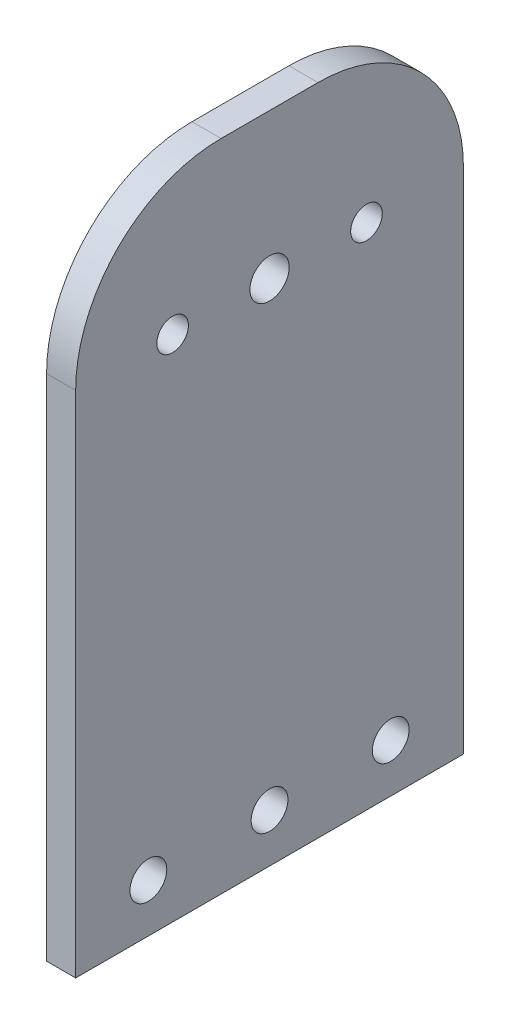
SolidWorks part; units mm, degrees
ref_plane "Front Plane" through (0, 0, 0) normal (0, 0, 1) x (1, 0, 0)
ref_plane "Top Plane" through (0, 0, 0) normal (0, 1, 0) x (1, 0, 0)
ref_plane "Right Plane" through (0, 0, 0) normal (1, 0, 0) x (0, 0, -1)
sketch "Sketch1" plane through (0, 0, 0) normal (1, 0, 0) x (0, 0, -1)
  line L1 (0, 0) -> (40, 0)
  line L2 (0, 0) -> (0, 52.5)
  line L3 (15, 67.5) -> (25, 67.5)
  line L4 (40, 0) -> (40, 52.5)
  arc A1 (25, 67.5) -> (40, 52.5) centre (25, 52.5) cw
  arc A2 (0, 52.5) -> (15, 67.5) centre (15, 52.5) cw
  point P7 (40, 67.5)
  point P10 (0, 67.5)
  dimension "D3" = 15
  dimension "D1" = 40
  dimension "D2" = 52.5
extrude "Boss-Extrude1" add sketch "Sketch1" along normal blind 3 contours L2 L1 L4 region at (0, 32.6224, -20)
ref_axis "Axis1" through (3, 67.5, -20) along (0, -1, 0)
ref_plane "Plane1" through (0, 0, -20) normal (0, 0, -1) x (-1, 0, 0)
hole_wizard "#6 Clearance Hole2" positions "Sketch6" profile "Sketch7" hole size "#6" standard "ANSI Inch" end condition through all
sketch "Sketch6" plane through (3, 0, 0) normal (1, 0, 0) x (0, 0, -1)
  line L0 (0, 0) -> (40, 0) construction
  line L1 (20, -49.3392) -> (20, 49.3392) construction
  point P0 (7.5, 5)
  point P2 (20, 5)
  point P8 (20, 0)
  point P11 (32.5, 5)
  dimension "D1" = 12.5
  dimension "D2" = 5
sketch "Sketch7" plane through (3, 5, -7.5) normal (0, 1, 0) x (0, 0, -1)
  line L0 (0, 0) -> (0, 3)
  line L1 (0, 3) -> (1.8986, 3)
  line L2 (1.8986, 3) -> (1.8986, 0)
  line L5 (1.8986, 0) -> (0, 0)
  line L11 (0, -6.35) -> (0, 107.95) construction
  dimension "Thru Hole Dia." = 3.7973
  dimension "Thru Hole Depth" = 3
sketch "Sketch10" plane through (3, 0, 0) normal (1, 0, 0) x (0, 0, -1)
  line L0 (0, 0) -> (40, 0) construction
  line L1 (20, 67.5) -> (20, -0.1097) construction
  circle A0 centre (20, 52.5) radius 2.025
  point P4 (0, 0)
  dimension "D2" = 4.05
  dimension "D1" = 52.5
extrude "Cut-Extrude1" cut sketch "Sketch10" against normal blind 10
hole_wizard "#4 Clearance Hole3" positions "Sketch11" profile "Sketch12" hole size "#4" standard "ANSI Inch" end condition through all
sketch "Sketch11" plane through (3, 0, 0) normal (1, 0, 0) x (0, 0, -1)
  line L0 (20, -49.3392) -> (20, 49.3392) construction
  circle A1 centre (20, 52.5) radius 2.025 construction
  point P0 (10, 52.5)
  point P5 (0, 0)
  point P8 (0, 0)
  point P12 (0, 0)
  point P13 (0, 0)
  point P16 (30, 52.5)
  dimension "D1" = 10
sketch "Sketch12" plane through (3, 52.5, -10) normal (0, 1, 0) x (0, 0, -1)
  line L0 (0, 0) -> (0, 3)
  line L1 (0, 3) -> (1.6319, 3)
  line L2 (1.6319, 3) -> (1.6319, 0)
  line L5 (1.6319, 0) -> (0, 0)
  line L11 (0, -6.35) -> (0, 107.95) construction
  dimension "Thru Hole Dia." = 3.2639
  dimension "Thru Hole Depth" = 3
equation "\"Shaft Height\"= 52.5mm"
equation "\"D2@Sketch1\"=\"Shaft Height\""
equation "\"D1@Sketch10\"=\"Shaft Height\""
